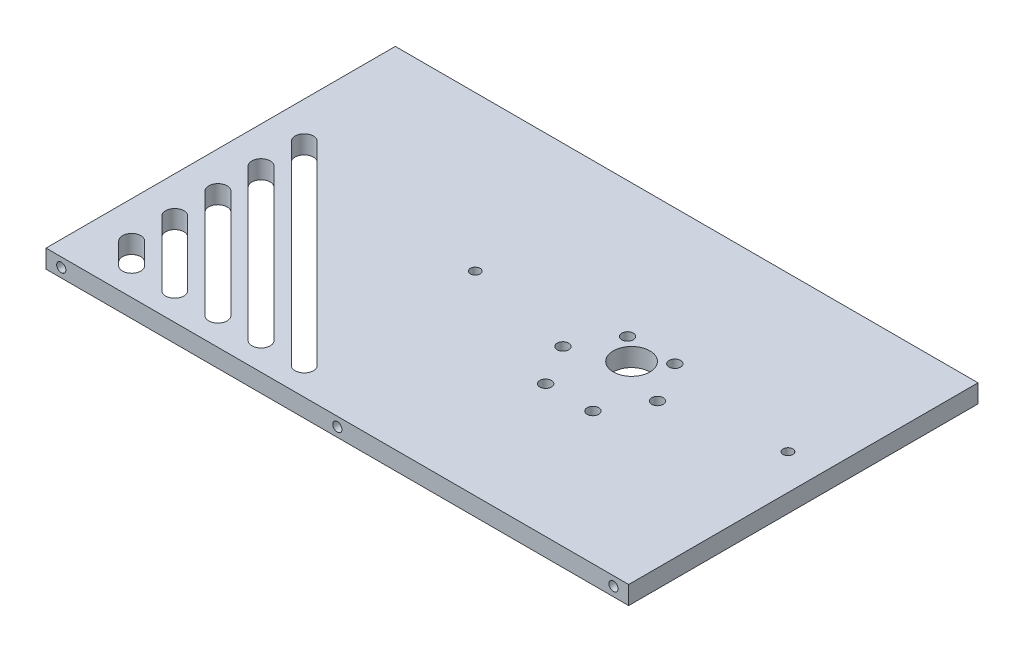
SolidWorks part; units mm, degrees
ref_plane "Front Plane" through (0, 0, 0) normal (1, 0, 0) x (0, 1, 0)
ref_plane "Top Plane" through (0, 0, 0) normal (0, 0, 1) x (0, 1, 0)
ref_plane "Right Plane" through (0, 0, 0) normal (0, 1, 0) x (-1, 0, 0)
sketch "Sketch1" plane through (0, 0, 0) normal (0, 1, 0) x (-1, 0, 0)
  line L3 (191, 0) -> (0, 0)
  line L10 (0, 114.5) -> (191, 114.5)
  line L15 (191, 114.5) -> (191, 0)
  line L17 (0, 114.5) -> (0, 0)
  point P0 (0, 0)
  point P16 (-5.5507, 58)
  point P19 (0, 0)
  point P27 (191, 0)
  dimension "D1" = 191
  dimension "D3" = 114.5
extrude "Boss-Extrude1" add sketch "Sketch1" along normal blind 6 contours L10 L17 L3 L15 region at (-95.5, 0, 57.25)
sketch "Sketch2" plane through (0, 0, 0) normal (0, -1, 0) x (1, 0, 0)
  line L0 (-113.4294, 6) -> (27.4505, 6) construction
  line L1 (-153.4835, 108.5) -> (20.1803, 108.5) construction
  line L2 (-48.0825, 39.2019) -> (29.2007, 39.2019) construction
  line L3 (-81.35, 53.663) -> (-81.35, 63.7746) construction
  line L4 (-191, 114.5) -> (-191, 0) construction
  line L7 (-44.35, 45.4394) -> (-44.35, 50045.4394) construction
  line L8 (-10, 10.8138) -> (-10, 44.7981) construction
  line L9 (-179, 84.2868) -> (-157.7868, 105.5) construction
  line L10 (-181.1213, 86.4081) -> (-159.9081, 107.6213)
  line L11 (-176.8787, 82.1655) -> (-155.6655, 103.3787)
  line L12 (-179, 70.1447) -> (-143.6447, 105.5) construction
  line L13 (-181.1213, 72.266) -> (-145.766, 107.6213)
  line L14 (-176.8787, 68.0233) -> (-141.5233, 103.3787)
  line L15 (-179, 56.0025) -> (-129.5025, 105.5) construction
  line L16 (-181.1213, 58.1238) -> (-131.6238, 107.6213)
  line L17 (-176.8787, 53.8812) -> (-127.3812, 103.3787)
  line L18 (-179, 41.8604) -> (-115.3604, 105.5) construction
  line L19 (-181.1213, 43.9817) -> (-117.4817, 107.6213)
  line L20 (-176.8787, 39.7391) -> (-113.2391, 103.3787)
  line L21 (-182, 120.5517) -> (-182, 16.1068) construction
  line L23 (-62.85, -5.1417) -> (-62.85, -109.5866) construction
  line L24 (-179, 98.4289) -> (-171.9289, 105.5) construction
  line L25 (-166.2721, 92.7721) -> (-163.4437, 89.9437) construction
  line L26 (-159.201, 85.701) -> (-156.3726, 82.8726) construction
  line L27 (-152.1299, 78.6299) -> (-149.3015, 75.8015) construction
  line L28 (-181.1213, 100.5503) -> (-174.0503, 107.6213)
  line L29 (-176.8787, 96.3076) -> (-169.8076, 103.3787)
  line L30 (-170.5147, 97.0147) -> (-173.3431, 99.8431) construction
  line L32 (-191, 0) -> (0, 0) construction
  line L33 (-62.85, 57.7019) -> (-62.85, -1.2686) construction
  line L35 (0, 114.5) -> (-191, 114.5) construction
  line L36 (0, 114.5) -> (0, 0) construction
  circle A7 centre (-62.85, 50.7019) radius 6
  circle A9 centre (-62.85, 57.7019) radius 18.5 construction
  arc A11 (-181.1213, 86.4081) -> (-176.8787, 82.1655) centre (-179, 84.2868) ccw
  arc A12 (-155.6655, 103.3787) -> (-159.9081, 107.6213) centre (-157.7868, 105.5) ccw
  arc A13 (-181.1213, 72.266) -> (-176.8787, 68.0233) centre (-179, 70.1447) ccw
  arc A14 (-141.5233, 103.3787) -> (-145.766, 107.6213) centre (-143.6447, 105.5) ccw
  arc A15 (-181.1213, 58.1238) -> (-176.8787, 53.8812) centre (-179, 56.0025) ccw
  arc A16 (-127.3812, 103.3787) -> (-131.6238, 107.6213) centre (-129.5025, 105.5) ccw
  arc A17 (-181.1213, 43.9817) -> (-176.8787, 39.7391) centre (-179, 41.8604) ccw
  arc A18 (-113.2391, 103.3787) -> (-117.4817, 107.6213) centre (-115.3604, 105.5) ccw
  arc A19 (-181.1213, 100.5503) -> (-176.8787, 96.3076) centre (-179, 98.4289) ccw
  arc A20 (-169.8076, 103.3787) -> (-174.0503, 107.6213) centre (-171.9289, 105.5) ccw
  circle A21 centre (-62.85, 57.7019) radius 15.5 construction
  circle A22 centre (-78.35, 57.7019) radius 1.9
  circle A23 centre (-70.6, 71.1253) radius 1.9
  circle A24 centre (-55.1, 71.1253) radius 1.9
  circle A25 centre (-47.35, 57.7019) radius 1.9
  circle A26 centre (-55.1, 44.2785) radius 1.9
  circle A27 centre (-70.6, 44.2785) radius 1.9
  circle A32 centre (-62.85, 50.7019) radius 51.25 construction
  circle A33 centre (-114.1, 50.7019) radius 1.6
  circle A34 centre (-62.85, 101.9519) radius 1.6 construction
  circle A35 centre (-11.6, 50.7019) radius 1.6
  circle A36 centre (-62.85, -0.5481) radius 1.6 construction
  point P19 (0, 0)
  point P20 (-57.85, 84.701)
  point P21 (-57.85, 86.8223)
  point P22 (0, 0)
  point P23 (-57.85, 57.1238)
  point P24 (-175.4645, 101.9645)
  point P45 (-168.3934, 94.8934)
  point P50 (-161.3223, 87.8223)
  point P57 (-154.2513, 80.7513)
  point P64 (-147.1802, 73.6802)
  dimension "D14" = 31
  dimension "D15" = 3.8
  dimension "D2" = 37
  dimension "D6" = 12
  dimension "D3" = 102.5
  dimension "D9" = 3.2
  dimension "D7" = 45
  dimension "D8" = 6
  dimension "D11" = 4
  dimension "D13" = 7
  dimension "D5" = 6
  dimension "D10" = 6
  dimension "D4" = 33.2019
  dimension "D17" = 10
  dimension "D19" = 10
  dimension "D20" = 9
  dimension "D16" = 6
  dimension "D18" = 4
extrude "Cut-Extrude1" cut sketch "Sketch2" against normal up to next
sketch "Sketch3" plane through (0, 0, 0) normal (0, 0, -1) x (1, 0, 0)
  line L2 (0, -3) -> (50000, -3) construction
  line L3 (0, -6) -> (0, 0) construction
  line L4 (-191, -6) -> (-191, 0) construction
  line L5 (-95.5, 0) -> (-95.5, -6) construction
  line L6 (-191, 0) -> (0, 0) construction
  line L7 (-191, -6) -> (0, -6) construction
  circle A0 centre (-5, -3) radius 1.5
  circle A1 centre (-186, -3) radius 1.5
  circle A2 centre (-95.5, -3) radius 1.5
  point P11 (0, -3)
  dimension "D1" = 3
  dimension "D3" = 5
  dimension "D2" = 5
extrude "Cut-Extrude2" cut sketch "Sketch3" against normal blind 20
extrude "Cut-Extrude3" cut sketch "Sketch3<3>" along normal blind 20 from surface starting at face at (-95.5, 3, 114.5)
sketch "Sketch3<3>" plane through (0, 0, 0) normal (0, 0, -1) x (1, 0, 0) same geometry as "Sketch3"
equation "\"MotorDriverLength\"= 60mm"
equation "\"MotorLength\"= 60"
equation "\"MotorDriverWidth\"=45"
equation "\"MotorWidth\"= 37"
equation "\"InnerWallThickness\"=3"
equation "\"BatteryWidth\"= 60"
equation "\"OuterWallThickness\" = 6"
equation "\"CompartmentHeight\"=37"
equation "\"CompartmentWidth\"= \"MotorDriverLength\""
equation "\"MotorDiameter\"=37"
equation "\"BatteryHeight\"=24.2019"
equation "\"MotorDriverHeight\"=20"
equation "\"CircuitHeight\"=30"
equation "\"FanThickness\"= 10"
equation "\"FanHeight\"=50"
equation "\"D1@Boss-Extrude1\" = \"OuterWallThickness\""
equation "\"MotorShaftHole\"=12"
equation "\"BearingBore\"=4"
equation "\"MinShinWidth\"= 20"
equation "\"ShinThickness\"=10"
equation "\"PivotDistance\"=40"
equation "\"ThighLength\"= 200"
equation "\"HipBore\"=27"
equation "\"ThighThickness\"=20"
equation "\"MaxBending\"=135"
equation "\"MaxStretchingAngle\"= 140"
equation "\"ThighJointDistance\"=157.485"
equation "\"ShinLength\"=100"
equation "\"BearingDiameter\"= 10"
equation "\"D2@Sketch2\"=\"MotorDiameter\""
equation "\"D6@Sketch2\"=\"MotorShaftHole\""
equation "\"D5@Sketch2\"=\"OuterWallThickness\""
equation "\"D10@Sketch2\"=\"OuterWallThickness\""
equation "\"D4@Sketch2\"=\"BatteryHeight\"+\"OuterWallThickness\"+\"InnerWallThickness\""
equation "\"GearboxDiameter\"=102.5"
equation "\"D1@Sketch1\" = \"ChessisInnerWidth\""
equation "\"ChessisInnerWidth\"= \"OuterWallThickness\" * 2 + \"MotorDriverLength\" * 2 + \"InnerWallThickness\" * 3 + \"CircuitLength\""
equation "\"CircuitLength\"=50"
equation "\"D3@Sketch1\"=\"GearboxDiameter\"+\"OuterWallThickness\"*2"
equation "\"D3@Sketch2\"=\"GearboxDiameter\""
equation "\"D17@Sketch2\"=\"OuterWallThickness\"+4"
equation "\"D20@Sketch2\"=\"OuterWallThickness\"+3"
